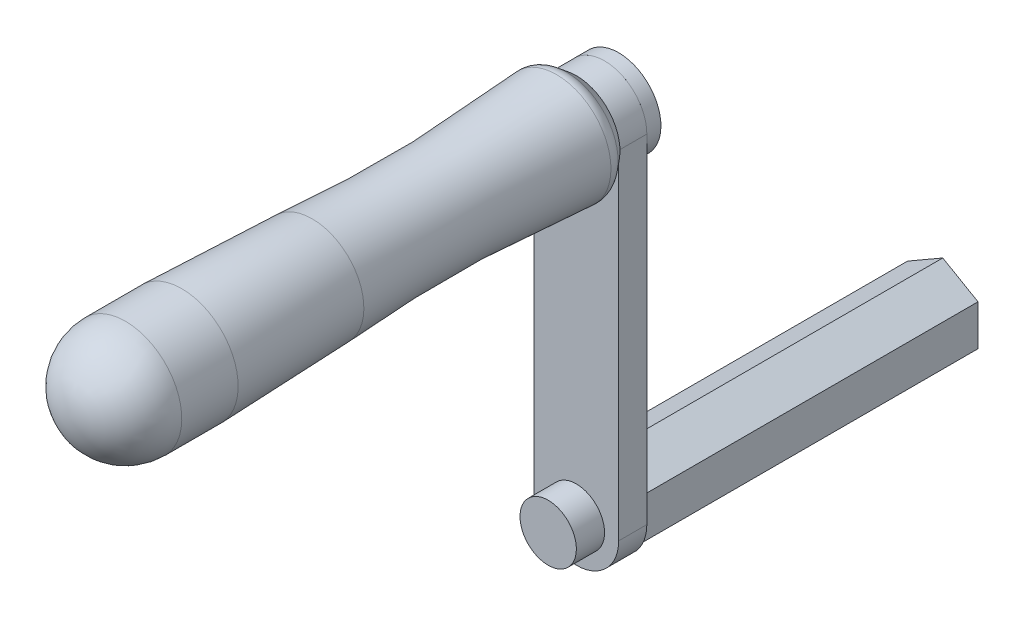
SolidWorks part; units mm, degrees
ref_plane "Front Plane" through (0, 0, 0) normal (0, 0, 1) x (1, 0, 0)
ref_plane "Top Plane" through (0, 0, 0) normal (0, 1, 0) x (1, 0, 0)
ref_plane "Right Plane" through (0, 0, 0) normal (1, 0, 0) x (0, 0, -1)
sketch "Sketch1" plane through (0, 0, 0) normal (0, 0, 1) x (1, 0, 0)
  line L1 (0, 9.1654) -> (-7.9375, 4.5827)
  line L2 (-7.9375, 4.5827) -> (-7.9375, -4.5827)
  line L3 (-7.9375, -4.5827) -> (0, -9.1654)
  line L4 (0, -9.1654) -> (7.9375, -4.5827)
  line L5 (7.9375, -4.5827) -> (7.9375, 4.5827)
  line L6 (7.9375, 4.5827) -> (0, 9.1654)
  circle A0 centre (0, 0) radius 7.9375 construction
  dimension "D1" = 15.875
extrude "Boss-Extrude1" add sketch "Sketch1" along normal mid plane 76.2
sketch "Sketch2" plane through (0, 0, 38.1) normal (0, 0, 1) x (1, 0, 0)
  circle A0 centre (0, 0) radius 3.175
  dimension "D1" = 6.35
extrude "Boss-Extrude2" add sketch "Sketch2" along normal blind 12.7
sketch "Sketch5" plane through (0, 0, 50.8) normal (0, 0, 1) x (1, 0, 0)
  circle A0 centre (0, 0) radius 6.35
  dimension "D1" = 12.7
extrude "Boss-Extrude4" add sketch "Sketch5" against normal blind 6.35
sketch "Sketch3" plane through (0, 0, 44.45) normal (0, 0, 1) x (1, 0, 0)
  line L0 (0, 0) -> (0, 76.2) construction
  line L1 (-9.525, 0) -> (-9.525, 76.2)
  line L2 (9.525, 0) -> (9.525, 76.2)
  arc A0 (-9.525, 0) -> (9.525, 0) centre (0, 0) ccw
  arc A1 (9.525, 76.2) -> (-9.525, 76.2) centre (0, 76.2) ccw
  circle A2 centre (0, 0) radius 3.175 construction
  circle A3 centre (0, 0) radius 3.175
  circle A4 centre (0, 76.2) radius 3.175
  point P3 (0, 38.1)
  dimension "D1" = 9.525
  dimension "D2" = 76.2
extrude "Boss-Extrude3" add sketch "Sketch3" against normal up to surface (6.35 mm away) separate body up to face at (3.175, 0, 38.1)
sketch "Sketch6" plane through (0, 0, 0) normal (1, 0, 0) x (0, 0, -1)
  line L2 (-38.1, 79.375) -> (-38.1, 85.725)
  line L3 (-38.1, 79.375) -> (-44.45, 79.375)
  line L4 (-38.1, 85.725) -> (-34.925, 85.725)
  line L5 (-34.925, 85.725) -> (-34.925, 76.2)
  line L6 (-34.925, 76.2) -> (-158.75, 76.2) construction
  line L8 (-146.05, 88.9) -> (-133.35, 88.9)
  line L9 (-44.45, 88.9) -> (-44.45, 79.375)
  line L10 (-133.35, 88.9) -> (-44.45, 88.9) construction
  line L13 (-38.1, 76.2) -> (-38.1, 85.725) construction
  line L14 (-34.925, 76.2) -> (-158.75, 76.2)
  arc A0 (-158.75, 76.2) -> (-146.05, 88.9) centre (-146.05, 76.2) cw
  arc A2 (-103.9621, 87.836) -> (-44.45, 88.9) centre (-80.0844, 417.1716) ccw
  arc A3 (-133.35, 88.9) -> (-103.9621, 87.836) centre (-133.35, -317.5) cw
  dimension "D6" = 406.4
  dimension "D7" = 330.2
  dimension "D1" = 19.05
  dimension "D2" = 3.175
  dimension "D3" = 123.825
  dimension "D4" = 25.4
  dimension "D5" = 12.7
revolve "Revolve1" add sketch "Sketch6" angle 360 about L6
chamfer "Chamfer1" distance 3.175 angle 45 1 edges at (0, 88.9, 44.45) first distance on face at (0, 87.836, 103.9621)
fillet "Fillet1" radius 3.175 1 edges at (12.371, 76.2, 47.6234)
